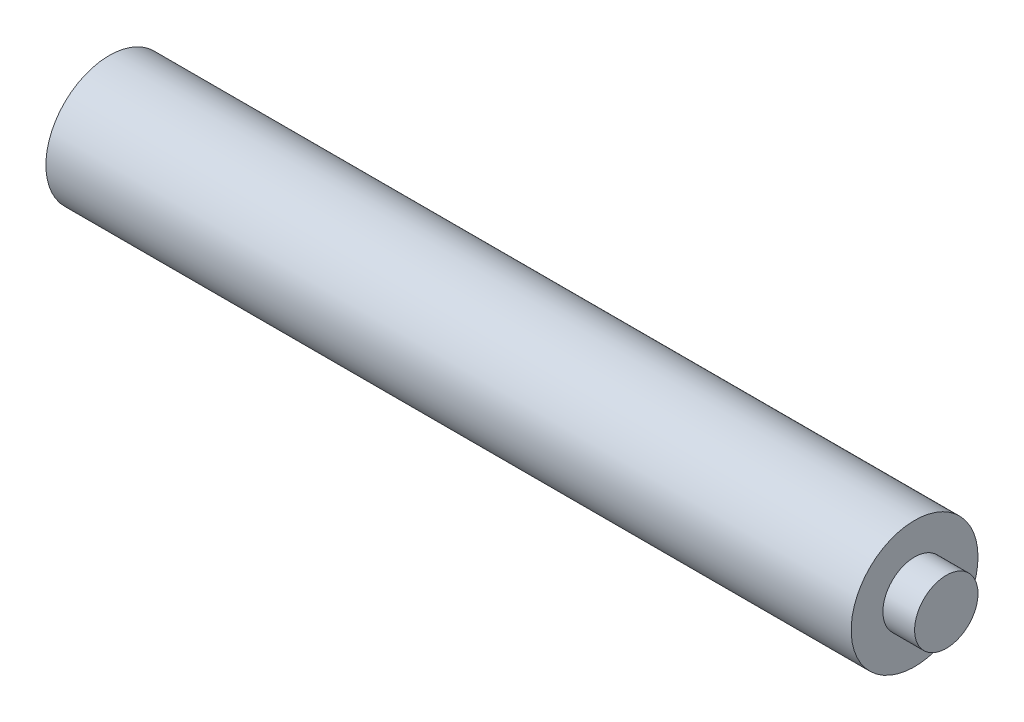
SolidWorks part; units mm, degrees
ref_plane "Front Plane" through (0, 0, 0) normal (0, 0, 1) x (1, 0, 0)
ref_plane "Top Plane" through (0, 0, 0) normal (0, 1, 0) x (1, 0, 0)
ref_plane "Right Plane" through (0, 0, 0) normal (1, 0, 0) x (0, 0, -1)
sketch "Sketch1" plane through (0, 0, 0) normal (1, 0, 0) x (0, 0, -1)
  circle A0 centre (0, 0) radius 4
  dimension "D1" = 8
extrude "Boss-Extrude1" add sketch "Sketch1" along normal mid plane 50.8
sketch "Sketch2" plane through (25.4, 0, 0) normal (1, 0, 0) x (0, 0, -1)
  circle A0 centre (0, 0) radius 2
  dimension "D1" = 4
extrude "Boss-Extrude2" add sketch "Sketch2" along normal blind 2
